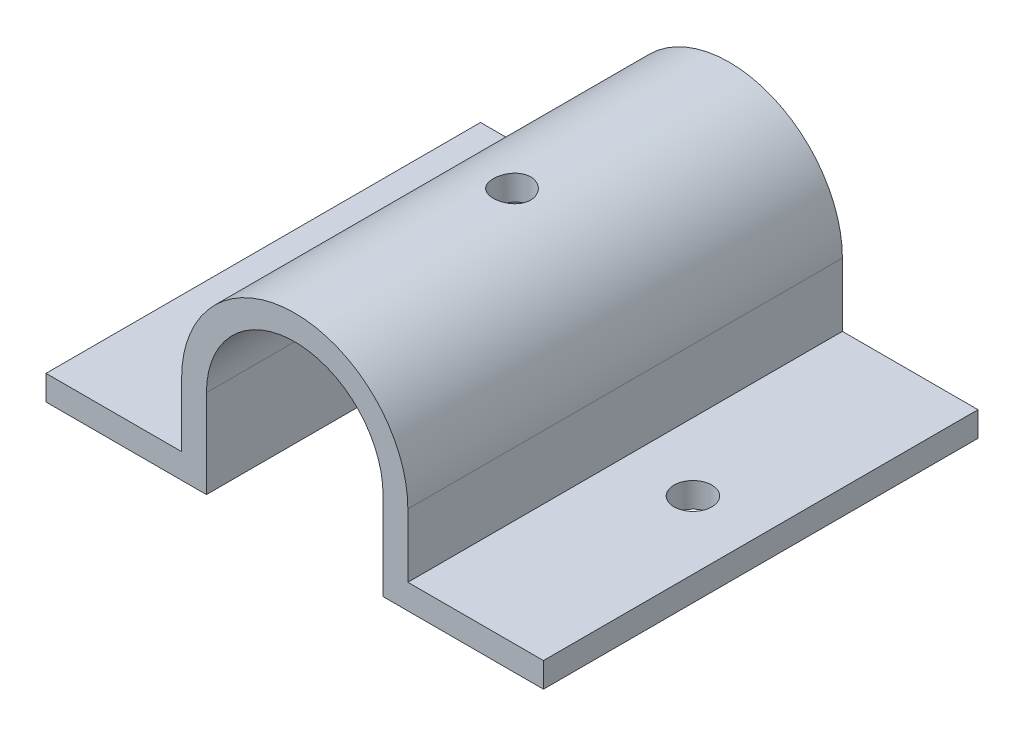
SolidWorks part; units mm, degrees
ref_plane "Front Plane" through (0, 0, 0) normal (0, 0, 1) x (1, 0, 0)
ref_plane "Top Plane" through (0, 0, 0) normal (0, 1, 0) x (1, 0, 0)
ref_plane "Right Plane" through (0, 0, 0) normal (1, 0, 0) x (0, 0, -1)
sketch "Sketch1" plane through (0, 0, 0) normal (0, 0, 1) x (1, 0, 0)
  line L0 (-40.068, 0) -> (-18.224, 0)
  line L1 (-18.224, 0) -> (-18.224, 28.448)
  line L2 (-18.224, 28.448) -> (18.224, 28.448)
  line L3 (18.224, 28.448) -> (18.224, 0)
  line L4 (18.224, 0) -> (40.068, 0)
  line L5 (-40.068, -4) -> (-14.224, -4)
  line L6 (-14.224, -4) -> (-14.224, 24.448)
  line L7 (-14.224, 24.448) -> (14.224, 24.448)
  line L8 (14.224, 24.448) -> (14.224, -4)
  line L9 (14.224, -4) -> (40.068, -4)
  line L10 (-40.068, 0) -> (-40.068, -4)
  line L11 (40.068, 0) -> (40.068, -4)
  point P13 (0, 24.448)
  dimension "D1" = 21.844
  dimension "D2" = 4
  dimension "D3" = 21.844
  dimension "D4" = 28.448
  dimension "D5" = 28.448
extrude "Boss-Extrude1" add sketch "Sketch1" along normal blind 70
sketch "Sketch2" plane through (0, 0, 0) normal (0, 1, 0) x (1, 0, 0)
  line L0 (29.146, 0) -> (29.146, -70)
  line L3 (40.068, 0) -> (18.224, 0) construction
  line L4 (40.068, -70) -> (18.224, -70) construction
  circle A0 centre (-31.2803, -35) radius 3.048
  circle A1 centre (29.146, -35) radius 3.048
  dimension "D1" = 6.096
extrude "Cut-Extrude1" cut sketch "Sketch2" against normal blind 70 contours A0 | L0 A1 | L0 A1 region at (30.4396, 0, 35) region at (27.8524, 0, 35) region at (-31.2803, 0, 35)
fillet "Fillet1" 2 edges at (-14.224, 24.448, 35) (14.224, 24.448, 35) type full round first side face at (-14.224, 10.224, 35) second side face at (14.224, 10.224, 35) middle face at (0, 24.448, 35)
fillet "Fillet2" 2 edges at (-18.224, 28.448, 35) (18.224, 28.448, 35) type full round first side face at (-18.224, 14.224, 35) second side face at (18.224, 14.224, 35) middle face at (0, 28.448, 35)
sketch "Sketch3" plane through (0, 0, 0) normal (0, 1, 0) x (1, 0, 0)
  line L0 (-18.224, -70) -> (18.224, -70) construction
  line L1 (40.068, -70) -> (40.068, 0) construction
  circle A0 centre (0, -35) radius 3
  point P2 (0, 0)
  point P5 (0, -70)
  point P8 (40.068, -35)
  dimension "D1" = 6
extrude "Cut-Extrude2" cut sketch "Sketch3" along normal blind 70
